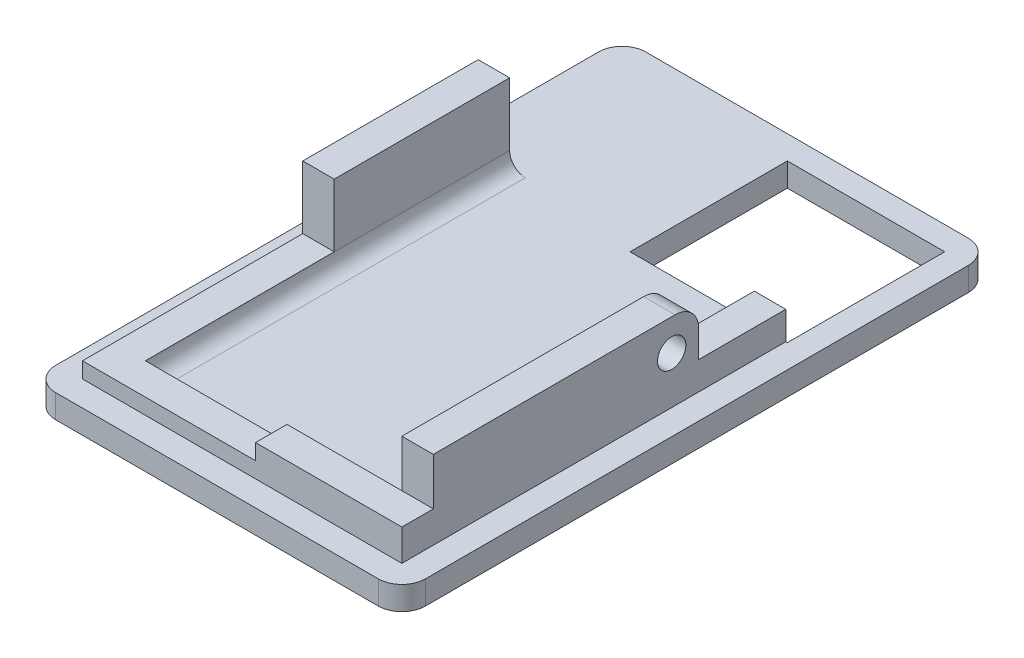
SolidWorks part; units mm, degrees
ref_plane "前视基准面" through (0, 0, 0) normal (0, 0, 1) x (1, 0, 0)
ref_plane "上视基准面" through (0, 0, 0) normal (0, 1, 0) x (1, 0, 0)
ref_plane "右视基准面" through (0, 0, 0) normal (1, 0, 0) x (0, 0, -1)
sketch "草图1" plane through (0, 0, 0) normal (0, 1, 0) x (1, 0, 0)
  line L1 (-11.75, 18.75) -> (11.75, 18.75)
  line L2 (-11.75, 18.75) -> (-11.75, -18.75)
  line L3 (-11.75, -18.75) -> (11.75, -18.75)
  line L4 (11.75, 18.75) -> (11.75, -18.75)
  dimension "D1" = 23.5
  dimension "D2" = 37.5
  dimension "D3" = 18.75
  dimension "D4" = 11.75
extrude "凸台-拉伸1" add sketch "草图1" along normal blind 1.5
fillet "圆角1" radius 1.5 4 edges at (-11.75, 0.75, -18.75) (11.75, 0.75, -18.75) (11.75, 0.75, 18.75) (-11.75, 0.75, 18.75)
sketch "草图2" plane through (0, 1.5, 0) normal (0, 1, 0) x (1, 0, 0)
  line L0 (-8.7921, -17.15) -> (10.15, -17.15)
  line L1 (-10.15, 8) -> (-8.15, 8)
  line L2 (-10.15, 8) -> (-10.15, -17.15)
  line L3 (-10.15, -17.15) -> (-8.7921, -17.15)
  line L4 (-8.15, 8) -> (-8.15, -15.15)
  line L5 (10.15, -17.15) -> (10.15, 8)
  line L6 (10.15, 8) -> (8.15, 8)
  line L7 (8.15, 8) -> (8.15, -15.15)
  line L8 (8.15, -15.15) -> (-8.15, -15.15)
  line L9 (-11.75, 17.25) -> (-11.75, -17.25) construction
  line L10 (11.75, -17.25) -> (11.75, 17.25) construction
  line L11 (10.25, 18.75) -> (-10.25, 18.75) construction
  line L12 (-10.25, -18.75) -> (10.25, -18.75) construction
  dimension "D1" = 1.6
  dimension "D2" = 1.6
  dimension "D3" = 10.75
  dimension "D4" = 1.6
  dimension "D5" = 25.15
  dimension "D6" = 2
  dimension "D7" = 2
  dimension "D8" = 2
extrude "凸台-拉伸2" add sketch "草图2" along normal blind 5
sketch "草图3" plane through (-10.15, 0, 0) normal (-1, 0, 0) x (0, 0, 1)
  line L1 (17.15, 6.5) -> (15.15, 6.5)
  line L2 (17.15, 6.5) -> (17.15, 2.5)
  line L3 (17.15, 2.5) -> (15.15, 2.5)
  line L4 (15.15, 6.5) -> (15.15, 2.5)
  dimension "D1" = 4
  dimension "D2" = 2
extrude "切除-拉伸1" cut sketch "草图3" against normal blind 11
sketch "草图4" plane through (0, 0, 15.15) normal (0, 0, 1) x (1, 0, 0)
  line L0 (0.85, 2.5) -> (-10.15, 2.5) construction
  line L1 (-10.15, 6.5) -> (-8.15, 6.5)
  line L2 (-10.15, 6.5) -> (-10.15, 2.5)
  line L3 (-10.15, 2.5) -> (-8.15, 2.5)
  line L4 (-8.15, 6.5) -> (-8.15, 2.5)
  line L5 (-8.15, 2.5) -> (-10.15, 2.5) construction
extrude "切除-拉伸2" cut sketch "草图4" against normal blind 12
sketch "草图5" plane through (0.85, 0, 0) normal (-1, 0, 0) x (0, 0, 1)
  line L0 (17.15, 2.5) -> (17.15, 6.5) construction
  line L1 (15.15, 6.5) -> (17.15, 6.5)
  line L2 (15.15, 6.5) -> (15.15, 3.5)
  line L3 (15.15, 3.5) -> (17.15, 3.5)
  line L4 (17.15, 6.5) -> (17.15, 3.5)
  dimension "D1" = 3
extrude "切除-拉伸3" cut sketch "草图5" against normal blind 12
fillet "圆角2" radius 1 3 edges at (0, 1.5, 15.15) (-8.15, 1.5, 3.575) (8.15, 1.5, 3.575)
sketch "草图6" plane through (10.15, 0, 0) normal (1, 0, 0) x (0, 0, -1)
  line L1 (-17.25, 1.5) -> (17.25, 1.5) construction
  circle A0 centre (0, 4.5) radius 0.9
  dimension "D1" = 3
extrude "切除-拉伸4" cut sketch "草图6" against normal blind 12
sketch "草图7" plane through (0, 0, 0) normal (0, -1, 0) x (1, 0, 0)
  line L0 (10.25, -18.75) -> (-10.25, -18.75) construction
  line L1 (0.25, -7.25) -> (10.25, -7.25)
  line L2 (0.25, -7.25) -> (0.25, -17.25)
  line L3 (0.25, -17.25) -> (10.25, -17.25)
  line L4 (10.25, -7.25) -> (10.25, -17.25)
  line L5 (11.75, 17.25) -> (11.75, -17.25) construction
  dimension "D1" = 1.5
  dimension "D2" = 10
  dimension "D3" = 10
  dimension "D4" = 1.5
extrude "切除-拉伸5" cut sketch "草图7" against normal blind 12
sketch "草图8" plane through (10.15, 0, 0) normal (1, 0, 0) x (0, 0, -1)
  line L1 (7.25, 6.5) -> (1.7165, 6.5)
  line L2 (7.25, 6.5) -> (7.25, 3.2855)
  line L3 (7.25, 3.2855) -> (1.7165, 3.2855)
  line L4 (1.7165, 6.5) -> (1.7165, 3.2855)
extrude "切除-拉伸6" cut sketch "草图8" against normal blind 10
fillet "圆角3" radius 1.5 1 edges at (9.15, 6.5, -1.7165)
